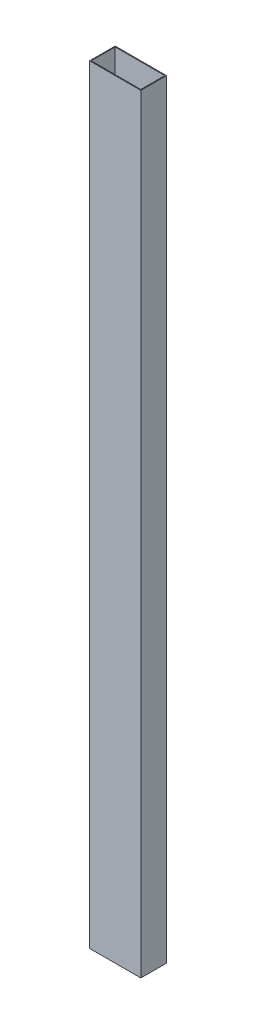
SolidWorks part; units mm, degrees
ref_plane "Front Plane" through (0, 0, 0) normal (0, 0, 1) x (1, 0, 0)
ref_plane "Top Plane" through (0, 0, 0) normal (0, 1, 0) x (1, 0, 0)
ref_plane "Right Plane" through (0, 0, 0) normal (1, 0, 0) x (0, 0, -1)
sketch "Sketch1" plane through (0, 0, 0) normal (0, 1, 0) x (1, 0, 0)
  line L1 (-25.4, -12.7) -> (25.4, -12.7)
  line L2 (-25.4, -12.7) -> (-25.4, 12.7)
  line L3 (-25.4, 12.7) -> (25.4, 12.7)
  line L4 (25.4, -12.7) -> (25.4, 12.7)
  line L5 (-25.4, -12.7) -> (25.4, 12.7) construction
  line L6 (-25.4, 12.7) -> (25.4, -12.7) construction
  point P0 (0, 0)
  dimension "D1" = 50.8
  dimension "D2" = 25.4
extrude "Boss-Extrude1" add sketch "Sketch1" along normal blind 762
sketch "Sketch2" plane through (0, 0, 0) normal (0, -1, 0) x (1, 0, 0)
  line L1 (-24.5999, 11.8999) -> (24.5999, 11.8999)
  line L2 (-24.5999, 11.8999) -> (-24.5999, -11.8999)
  line L3 (-24.5999, -11.8999) -> (24.5999, -11.8999)
  line L4 (24.5999, 11.8999) -> (24.5999, -11.8999)
  line L5 (-24.5999, 11.8999) -> (24.5999, -11.8999) construction
  line L6 (-24.5999, -11.8999) -> (24.5999, 11.8999) construction
  point P0 (0, 0)
  dimension "D1" = 49.1998
  dimension "D2" = 23.7998
extrude "Cut-Extrude1" cut sketch "Sketch2" against normal through all
